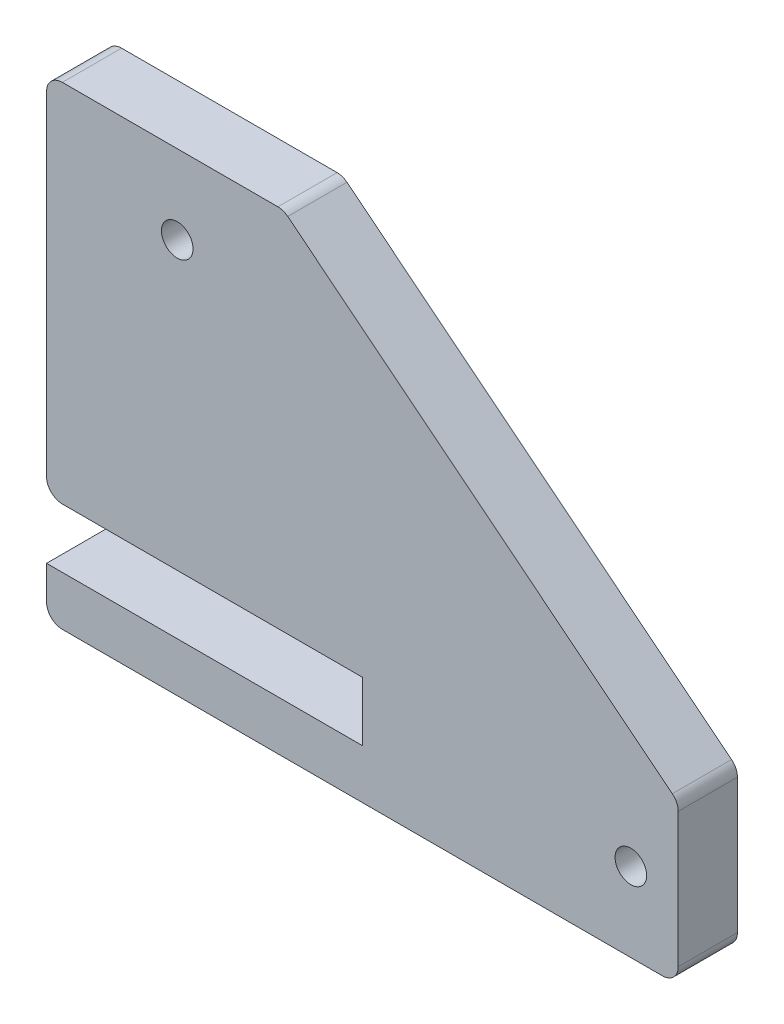
SolidWorks part; units mm, degrees
ref_plane "Front Plane" through (0, 0, 0) normal (0, 0, 1) x (1, 0, 0)
ref_plane "Top Plane" through (0, 0, 0) normal (0, 1, 0) x (1, 0, 0)
ref_plane "Right Plane" through (0, 0, 0) normal (1, 0, 0) x (0, 0, -1)
sketch "Sketch1" plane through (0, 0, 0) normal (0, 0, 1) x (1, 0, 0)
  line L0 (-25.4, 2.3813) -> (-25.4, 6.35)
  line L1 (-25.4, -2.3813) -> (0, -2.3813)
  line L3 (-25.4, 2.3813) -> (0, 2.3813)
  line L4 (0, -2.3813) -> (0, 2.3813)
  line L5 (-25.4, 6.35) -> (25.4, 6.35)
  line L6 (0, 0) -> (25.4, 0) construction
  line L7 (25.4, 6.35) -> (25.4, -6.35)
  line L8 (-25.4, -6.35) -> (25.4, -6.35)
  line L9 (-25.4, -2.3813) -> (-25.4, -6.35)
  line L11 (-25.4, 6.35) -> (25.4, 6.35)
  line L12 (-25.4, 6.35) -> (-25.4, 31.75)
  line L13 (-25.4, 31.75) -> (25.4, 31.75)
  line L14 (25.4, 6.35) -> (25.4, 31.75)
  dimension "D1" = 25.4
  dimension "D2" = 4.7625
  dimension "D3" = 25.4
  dimension "D4" = 12.7
  dimension "D5" = 38.1
extrude "Boss-Extrude1" add sketch "Sketch1" along normal mid plane 4.7625 contours L5 L14 L13 L12 | L6 L4 L1 L9 L8 L7 | L4 L6 L7 L5 L0 L3 region at (2.9308, 3.6329, 0) region at (0, 19.05, 0) region at (2.9308, -3.6329, 0)
sketch "Sketch2" plane through (0, 0, 2.3813) normal (0, 0, 1) x (1, 0, 0)
  line L0 (0, 0) -> (25.4, 0) construction
  line L2 (25.4, -6.35) -> (25.4, 31.75) construction
  circle A0 centre (21.59, 0) radius 1.27
  dimension "D1" = 2.54
  dimension "D2" = 2.54
extrude "Cut-Extrude1" cut sketch "Sketch2" against normal through all
sketch "Sketch3" plane through (0, 0, 2.3813) normal (0, 0, 1) x (1, 0, 0)
  circle A0 centre (-14.888, 25.4) radius 1.27
  circle A1 centre (21.59, 0) radius 1.27 construction
  dimension "D1" = 44.45
  dimension "D2" = 25.4
extrude "Cut-Extrude2" cut sketch "Sketch3" against normal through all
sketch "Sketch4" plane through (0, 0, 2.3813) normal (0, 0, 1) x (1, 0, 0)
  line L0 (-6.35, 31.75) -> (25.4, 6.35)
  line L1 (-25.4, 31.75) -> (25.4, 31.75) construction
  line L2 (25.4, -6.35) -> (25.4, 31.75) construction
  line L3 (-6.35, 31.75) -> (25.4, 31.75)
  line L4 (25.4, 31.75) -> (25.4, 6.35)
  dimension "D1" = 25.4
  dimension "D2" = 31.75
extrude "Cut-Extrude3" cut sketch "Sketch4" against normal through all
fillet "Fillet1" radius 1.27 6 edges at (-25.4, -6.35, 0) (25.4, -6.35, 0) (-25.4, 2.3813, 0) (-25.4, 31.75, 0) (25.4, 6.35, 0) (-6.35, 31.75, 0)
equation "\"D2@Sketch1\"=\"thick@FullAssem.Assembly\""
equation "\"D1@Sketch2\"=\"rodThick@FullAssem.Assembly\""
equation "\"D1@Boss-Extrude1\"=\"thick@FullAssem.Assembly\""
